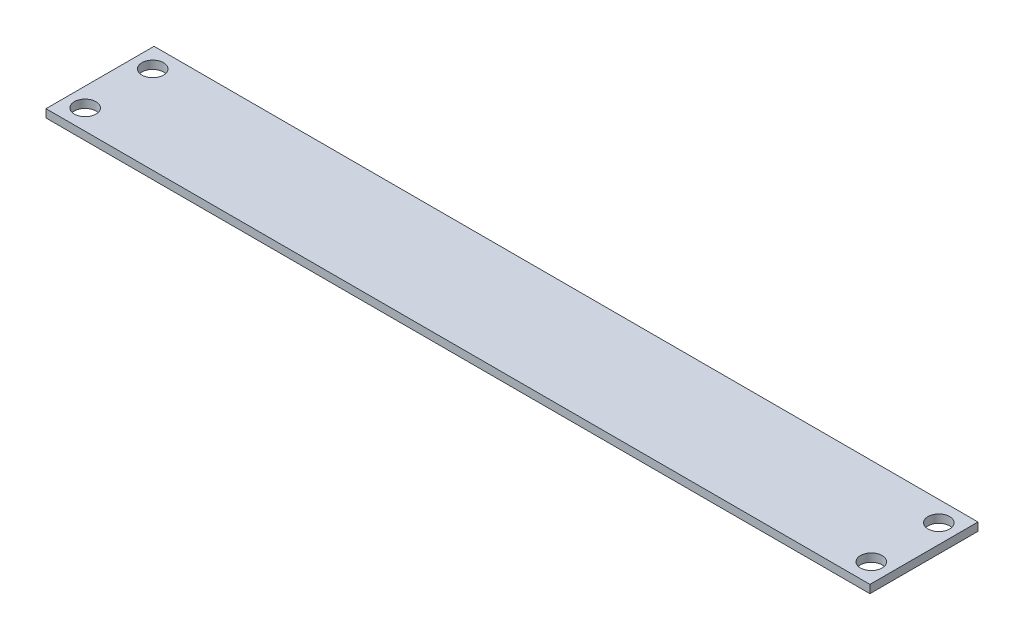
SolidWorks part; units mm, degrees
ref_plane "Front Plane" through (0, 0, 0) normal (0, 0, 1) x (1, 0, 0)
ref_plane "Top Plane" through (0, 0, 0) normal (0, 1, 0) x (1, 0, 0)
ref_plane "Right Plane" through (0, 0, 0) normal (1, 0, 0) x (0, 0, -1)
sketch "Sketch1" plane through (0, 0, 0) normal (0, 1, 0) x (1, 0, 0)
  line L1 (0, 0) -> (305, 0)
  line L2 (0, 0) -> (0, 40)
  line L3 (0, 40) -> (305, 40)
  line L4 (305, 0) -> (305, 40)
  circle A0 centre (7, 32.5) radius 4
  circle A1 centre (7, 7.5) radius 4
  circle A2 centre (298, 32.5) radius 4
  circle A3 centre (298, 7.5) radius 4
  point P13 (0, 0)
  dimension "D3" = 8
  dimension "D4" = 8
  dimension "D6" = 8
  dimension "D7" = 8
  dimension "D1" = 40
  dimension "D2" = 305
  dimension "D5" = 25
  dimension "D8" = 25
  dimension "D9" = 291
  dimension "D10" = 7
  dimension "D11" = 7.5
  dimension "D12" = 7.5
base flange "Base-Flange1" sketch "Sketch1" thickness 3 reverse thickness direction no parameters "D1"=2
sketch "Bend-Lines1" [suppressed] plane through (0, 0, 0) normal (0, 1, 0) x (1, 0, 0)
sketch "Bounding-Box1" [suppressed] plane through (0, 0, 0) normal (0, 1, 0) x (1, 0, 0)
sheet metal parameters "Sheet-Metal1" thickness 3 parameters "D1"=2
flat pattern "Flat-Pattern1" [suppressed]
sketch "Bend-Lines2" plane through (0, 0, 0) normal (0, 1, 0) x (1, 0, 0)
sketch3d "Bounding-Box2" [suppressed]
  line L0 (-305, 40, 0) -> (0, 40, 0) construction
  line L1 (-305, 0, 0) -> (0, 0, 0) construction
  line L2 (-305, 40, 0) -> (-305, 0, 0) construction
  line L3 (0, 40, 0) -> (0, 0, 0) construction
